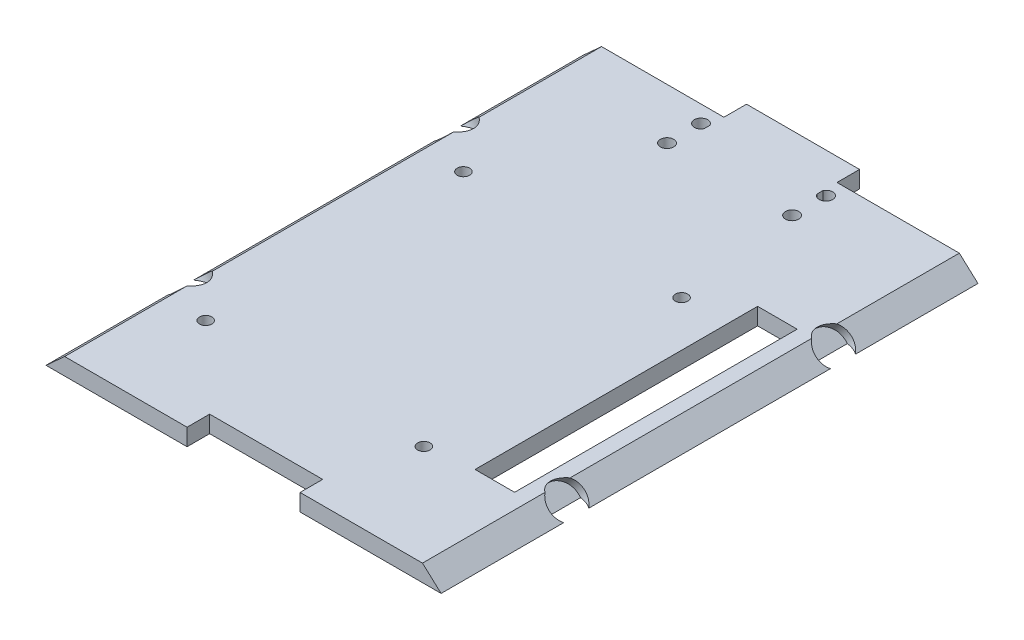
SolidWorks part; units mm, degrees
ref_plane "Front Plane" through (0, 0, 0) normal (0, 0, 1) x (1, 0, 0)
ref_plane "Top Plane" through (0, 0, 0) normal (0, 1, 0) x (1, 0, 0)
ref_plane "Right Plane" through (0, 0, 0) normal (1, 0, 0) x (0, 0, -1)
sketch "Sketch1" plane through (0, 0, 0) normal (0, 0, 1) x (1, 0, 0)
  line L0 (0, 0) -> (0, 44.45) construction
  line L1 (-40.2039, 5.9378) -> (40.2039, 5.9378)
  line L2 (-44.399, 2.1278) -> (44.399, 2.1278)
  line L3 (-40.2039, 5.9378) -> (-44.399, 2.1278)
  line L4 (40.2039, 5.9378) -> (44.399, 2.1278)
  arc A0 (44.399, 2.1278) -> (-44.399, 2.1278) centre (0, 0) ccw construction
  arc A1 (40.2039, 5.9378) -> (-40.2039, 5.9378) centre (0, 0) ccw construction
  dimension "D1" = 88.9
  dimension "D2" = 3.81
  dimension "D3" = 3.81
extrude "Boss-Extrude1" add sketch "Sketch1" along normal blind 120.65
sketch "Sketch2" plane through (0, 2.1278, 0) normal (0, -1, 0) x (1, 0, 0)
  line L0 (0, 120.65) -> (0, 0) construction
  line L1 (-34.417, 100.33) -> (20.701, 100.33) construction
  line L2 (-34.417, 100.33) -> (-34.417, 15.24) construction
  line L3 (-34.417, 15.24) -> (20.701, 15.24) construction
  line L4 (20.701, 100.33) -> (20.701, 15.24) construction
  line L5 (-44.399, 120.65) -> (44.399, 120.65) construction
  line L6 (-44.399, 0) -> (44.399, 0) construction
  line L7 (-34.417, 57.785) -> (20.701, 57.785) construction
  line L8 (-6.858, 100.33) -> (-6.858, 15.24) construction
  line L9 (40.2039, 120.65) -> (-40.2039, 120.65) construction
  line L10 (40.2039, 0) -> (-40.2039, 0) construction
  line L11 (0, -14.38) -> (0, 29.62) construction
  line L12 (19.05, -14.38) -> (-19.05, -14.38) construction
  line L13 (19.05, -14.38) -> (19.05, 29.62) construction
  line L14 (19.05, 29.62) -> (-19.05, 29.62) construction
  line L15 (-19.05, -14.38) -> (-19.05, 29.62) construction
  line L16 (19.05, 7.62) -> (-19.05, 7.62) construction
  circle A0 centre (-31.369, 97.79) radius 1.397
  circle A1 centre (17.653, 39.878) radius 1.397
  circle A2 centre (-31.369, 39.878) radius 1.397
  circle A3 centre (17.653, 97.79) radius 1.397
  circle A4 centre (-14.05, 11.43) radius 1.5
  circle A5 centre (14.05, 3.81) radius 1.5
  circle A6 centre (-14.05, 3.81) radius 1.5
  circle A8 centre (14.05, 11.43) radius 1.5
  point P10 (-6.858, 100.33)
  dimension "D4" = 2.794
  dimension "D7" = 2.794
  dimension "D8" = 57.912
  dimension "D9" = 22.86
  dimension "D5" = 49.022
  dimension "D12" = 3.81
  dimension "D1" = 6.858
  dimension "D2" = 85.09
  dimension "D3" = 15.24
  dimension "D6" = 55.118
  dimension "D10" = 3.81
  dimension "D13" = 0
extrude "Cut-Extrude1" cut sketch "Sketch2" against normal through all
sketch "Sketch3" plane through (0, 2.1278, 0) normal (0, -1, 0) x (1, 0, 0)
  line L0 (0, 120.65) -> (0, 0) construction
  line L1 (-44.399, 120.65) -> (44.399, 120.65) construction
  line L2 (-44.399, 0) -> (44.399, 0) construction
  line L3 (0, 60.325) -> (44.399, 60.325) construction
  line L4 (-12.7, 120.65) -> (12.7, 120.65)
  line L5 (-12.7, 120.65) -> (-12.7, 115.57)
  line L6 (-12.7, 115.57) -> (12.7, 115.57)
  line L7 (12.7, 120.65) -> (12.7, 115.57)
  line L8 (44.399, 120.65) -> (44.399, 0) construction
  line L9 (0, 60.325) -> (-44.399, 60.325) construction
  line L10 (-44.399, 120.65) -> (-44.399, 0) construction
  line L11 (12.7, 0) -> (12.7, 5.08)
  line L12 (-12.7, 5.08) -> (12.7, 5.08)
  line L13 (-12.7, 0) -> (12.7, 0)
  line L14 (-12.7, 0) -> (-12.7, 5.08)
  point P10 (12.7, 118.11)
  dimension "D1" = 25.4
  dimension "D2" = 12.7
  dimension "D3" = 5.08
extrude "Cut-Extrude2" cut sketch "Sketch3" against normal through all
sketch "Sketch5" plane through (0, 2.1278, 0) normal (0, -1, 0) x (1, 0, 0)
  line L0 (12.7, 0) -> (12.7, 3.1562) construction
  line L1 (12.7, 5.08) -> (-12.7, 5.08)
  line L2 (12.7, 5.08) -> (12.7, -5.08)
  line L3 (12.7, -5.08) -> (-12.7, -5.08)
  line L4 (-12.7, 5.08) -> (-12.7, -5.08)
  line L5 (12.7, 5.08) -> (-12.7, 5.08) construction
  line L6 (40.2039, 0) -> (12.7, 0) construction
  dimension "D1" = 0
  dimension "D2" = 25.4
  dimension "D3" = 10.16
  dimension "D4" = 5.08
extrude "Boss-Extrude3" add sketch "Sketch5" against normal blind 3.81
sketch "Sketch6" plane through (0, 2.1278, 0) normal (0, -1, 0) x (1, 0, 0)
  line L0 (12.7, 120.65) -> (44.399, 120.65) construction
  line L1 (27.889, 96.52) -> (36.779, 96.52)
  line L2 (27.889, 96.52) -> (27.889, 33.02)
  line L3 (27.889, 33.02) -> (36.779, 33.02)
  line L4 (36.779, 96.52) -> (36.779, 33.02)
  line L5 (44.399, 120.65) -> (44.399, 0) construction
  dimension "D1" = 24.13
  dimension "D2" = 7.62
  dimension "D3" = 63.5
  dimension "D4" = 8.89
extrude "Cut-Extrude3" cut sketch "Sketch6" against normal through all
sketch "Sketch7" plane through (21.1272, 23.263, 0) normal (0.6723, 0.7403, 0) x (0.7403, -0.6723, 0)
  line L0 (28.6033, -120.65) -> (28.6033, 0) construction
  line L1 (31.4368, -120.65) -> (25.7698, -120.65) construction
  line L2 (25.7698, -60.325) -> (31.987, -60.325) construction
  line L3 (25.7698, -120.65) -> (25.7698, 0) construction
  circle A0 centre (28.6033, -90.297) radius 4
  circle A1 centre (28.6033, -30.353) radius 4
  dimension "D1" = 8
  dimension "D2" = 29.972
  dimension "D3" = 120.65
extrude "Cut-Extrude4" cut sketch "Sketch7" against normal blind 2
sketch "Sketch8" plane through (-21.1272, 23.263, 0) normal (-0.6723, 0.7403, 0) x (0.7403, 0.6723, 0)
  line L0 (-28.6033, 0) -> (-28.6033, -120.65) construction
  line L1 (-25.7698, 0) -> (-31.4368, 0) construction
  line L2 (-25.7698, -60.325) -> (-31.4368, -60.325) construction
  line L3 (-25.7698, -120.65) -> (-25.7698, 0) construction
  line L4 (-31.4368, -120.65) -> (-31.4368, 0) construction
  circle A0 centre (-28.6033, -30.353) radius 4
  circle A1 centre (-28.6033, -90.297) radius 4
  dimension "D1" = 8
  dimension "D2" = 29.972
  dimension "D3" = 120.65
extrude "Cut-Extrude5" cut sketch "Sketch8" against normal blind 2
